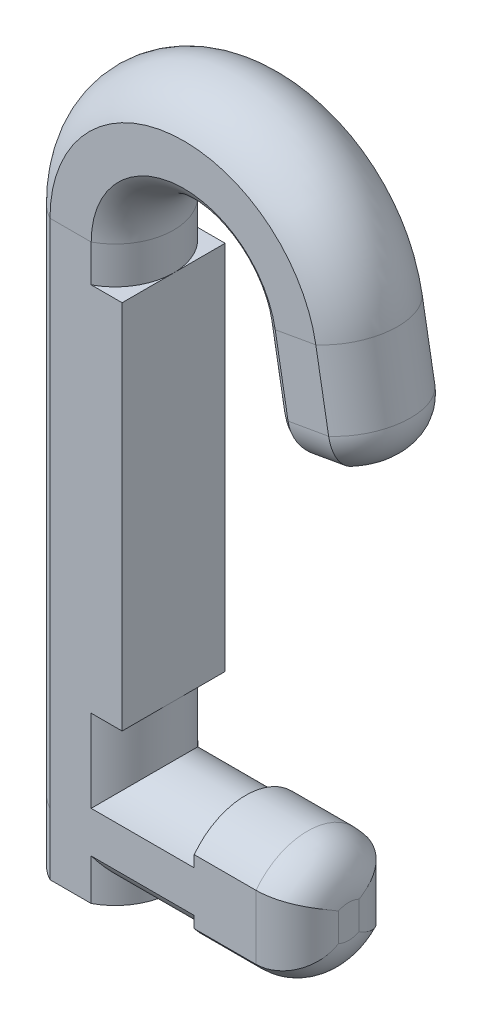
SolidWorks part; units mm, degrees
ref_plane "前视基准面" through (0, 0, 0) normal (0, 0, 1) x (1, 0, 0)
ref_plane "上视基准面" through (0, 0, 0) normal (0, 1, 0) x (1, 0, 0)
ref_plane "右视基准面" through (0, 0, 0) normal (1, 0, 0) x (0, 0, -1)
other "Configuration Table"
sketch "草图1" plane through (0, 0, 0) normal (0, 0, 1) x (1, 0, 0)
  line L0 (0, 0) -> (0, 24.8)
  line L1 (10.9164, 25.7551) -> (11.8862, 20.2551)
  line L2 (0, 0) -> (0, -3)
  arc A0 (0, 24.8) -> (10.9164, 25.7551) centre (5.5, 24.8) cw
  dimension "D1" = 5.5
  dimension "D2" = 10
  dimension "D3" = 24.8
  dimension "6" = 5.5
ref_plane "基准面3" through (0, -3, 0) normal (0, 1, 0) x (1, 0, 0)
sketch "草图13" plane through (0, -3, 0) normal (0, 1, 0) x (1, 0, 0)
  line L1 (-1, -2.5) -> (1, -2.5)
  line L3 (-1, 2.5) -> (1, 2.5)
  line L5 (-1, -2.5) -> (1, 2.5) construction
  line L6 (-1, 2.5) -> (1, -2.5) construction
  line L7 (0, 2.5) -> (0, -2.5) construction
  line L8 (1, 2.5) -> (1, -2.5) construction
  arc A0 (1, 2.5) -> (1, -2.5) centre (-0.3333, 0) cw
  arc A1 (-1, 2.5) -> (-1, -2.5) centre (0.3333, 0) ccw
  point P11 (1, 0)
  point P12 (2.5, 0)
  point P21 (0, 0)
  dimension "D2" = 2
  dimension "D1" = 5
  dimension "D3" = 1.5
sweep "扫描2" add profiles "草图13" path "草图1"
sketch "草图15" plane through (0, 0, 0) normal (0, 0, 1) x (1, 0, 0)
  line L0 (10.9164, 25.7551) -> (11.8862, 20.2551) construction
  line L1 (0, 0) -> (0, 24.8) construction
  line L3 (10.9164, 25.7551) -> (11.8862, 20.2551) construction
  line L4 (0, 0) -> (0, 24.8) construction
  line L5 (0, 0) -> (11, 0)
  arc A0 (10.9164, 25.7551) -> (0, 24.8) centre (5.5, 24.8) ccw construction
  arc A2 (10.9164, 25.7551) -> (0, 24.8) centre (5.5, 24.8) ccw construction
  dimension "D1" = 11
ref_plane "基准面2" through (11, 0, 0) normal (1, 0, 0) x (0, 0, -1)
sketch "草图16" plane through (11, 0, 0) normal (1, 0, 0) x (0, 0, -1)
  line L2 (-2.5, 0) -> (2.5, 0) construction
  line L4 (-2.5, -1) -> (-2.5, 1)
  line L6 (2.5, -1) -> (2.5, 1)
  line L7 (-2.5, -1) -> (2.5, 1) construction
  line L8 (-2.5, 1) -> (2.5, -1) construction
  line L9 (-2.5, -1) -> (2.5, -1) construction
  arc A3 (-2.5, -1) -> (2.5, -1) centre (0, 0.3333) ccw
  arc A4 (-2.5, 1) -> (2.5, 1) centre (0, -0.3333) cw
  point P0 (0, 0)
  point P9 (0, -2.5)
  dimension "D1" = 2
  dimension "D2" = 1.5
  dimension "D3" = 5
sweep "扫描4" add profiles "草图16" path "草图15"
sketch "草图17" plane through (11, 0, 0) normal (1, 0, 0) x (0, 0, -1)
  line L0 (-2.5, 1) -> (-2.5, -1) construction
  line L1 (-2.5, 1.5555) -> (-2.5, -1.5555)
  line L2 (2.5, -1) -> (2.5, 1) construction
  line L3 (2.5, -1) -> (2.5, 1) construction
  line L6 (2.5, 1.5555) -> (2.5, -1.5555)
  line L7 (2.5, 24.8) -> (2.5, 0) construction
  line L10 (-2.8, 1.073) -> (-2.8, -1.073)
  line L11 (2.8, -1.073) -> (2.8, 1.073)
  line L12 (-2.5, 0) -> (2.5, 0) construction
  arc A0 (2.5, -1.5555) -> (-2.5, -1.5555) centre (0, 0.3333) cw
  arc A15 (2.8, 1.073) -> (-2.8, 1.073) centre (0, -0.3333) ccw
  arc A16 (-2.8, -1.073) -> (2.8, -1.073) centre (0, 0.3333) ccw
  arc A17 (2.5, 1.5555) -> (-2.5, 1.5555) centre (0, -0.3333) ccw
  dimension "D1" = 0.3
extrude "凸台-拉伸1" add sketch "草图17" against normal blind 5
ref_plane "基准面4" through (1, 0, 0) normal (1, 0, 0) x (0, 0, -1)
sketch "草图19" plane through (1, 0, 0) normal (1, 0, 0) x (0, 0, -1)
  line L1 (-2.5, 5) -> (2.5, 5)
  line L2 (2.5, 0) -> (2.5, 24.8)
  line L3 (-2.5, 24.8) -> (-2.5, 0)
  line L4 (2.5, 5) -> (2.5, 23)
  line L5 (-2.5, 23) -> (-2.5, 5)
  line L6 (-2.5, 23) -> (2.5, 23)
  line L7 (0, 0) -> (0, 23) construction
  line L11 (2.5, 24.8) -> (-2.5, 24.8)
  line L12 (-2.5, 0) -> (2.5, 0)
  dimension "D2" = 18
  dimension "D3" = 5
  dimension "D1" = 0
extrude "凸台-拉伸2" add sketch "草图19" along normal blind 1.5
fillet "圆角2" radius 2 8 edges at (11.8862, 20.2551, 2.5) (14.3483, 20.6892, 0) (11.8862, 20.2551, -2.5) (9.4242, 19.8209, 0) (11, -2.8, 0) (11, 0, 2.5) (11, 2.8, 0) (11, 0, -2.5)
